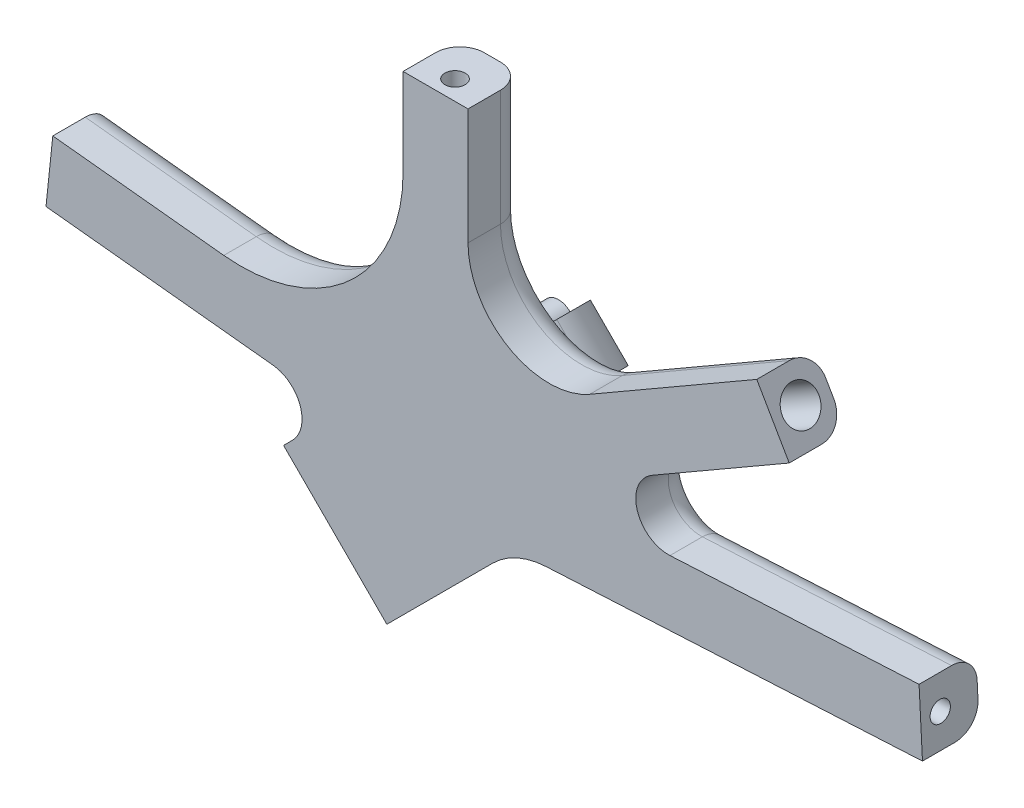
SolidWorks part; units mm, degrees
ref_plane "前基準面" through (0, 0, 0) normal (0, 0, 1) x (1, 0, 0)
ref_plane "上基準面" through (0, 0, 0) normal (0, 1, 0) x (1, 0, 0)
ref_plane "右基準面" through (0, 0, 0) normal (1, 0, 0) x (0, 0, -1)
sketch "草圖1" plane through (0, 0, 0) normal (0, 0, 1) x (1, 0, 0)
  line L0 (-27, 0) -> (-9.7279, 0) construction
  line L1 (-27, 2.7903) -> (-8.8458, 0.8822)
  line L2 (1.8837, -1.1163) -> (27, 0.2)
  line L3 (-27, 2.7903) -> (-26.5819, 6.7683)
  line L4 (-26.5819, 6.7683) -> (-5, 4.5)
  line L5 (3.1228, 2.9541) -> (26.7907, 4.1945)
  line L6 (26.7907, 4.1945) -> (27, 0.2)
  line L7 (-1, 5.1927) -> (16.7907, 15.4641)
  line L8 (16.7907, 15.4641) -> (18.7907, 12)
  line L9 (18.7907, 12) -> (3.1228, 2.9541)
  line L10 (-5, 4.5) -> (-5, 21)
  line L11 (-5, 21) -> (-1, 21)
  line L12 (-1, 21) -> (-1, 5.1927)
  line L13 (-8.8458, 0.8822) -> (-12.364, -2.636)
  line L14 (-12.364, -2.636) -> (-6, -9)
  line L15 (-6, -9) -> (1.8837, -1.1163)
  line L17 (3, 0) -> (27, 0) construction
  point P19 (-9.7279, 0)
  dimension "D1" = 54
  dimension "D2" = 27
  dimension "D3" = 6
  dimension "D4" = 3
  dimension "D5" = 90
  dimension "D6" = 4
  dimension "D7" = 4
  dimension "D8" = 4.5
  dimension "D9" = 4
  dimension "D10" = 30
  dimension "D11" = 8
  dimension "D12" = 12
  dimension "D13" = 4
  dimension "D14" = 22
  dimension "D15" = 135
  dimension "D16" = 90
  dimension "D17" = 9
  dimension "D18" = 21
  dimension "D19" = 16.5
  dimension "D20" = 0.2
  dimension "D21" = 9
extrude "填料-伸長1" add sketch "草圖1" along normal blind 3.5
fillet "圓角1" radius 5 2 edges at (1.8837, -1.1163, 1.75) (-1, 5.1927, 1.75)
fillet "圓角2" radius 2 2 edges at (-8.8458, 0.8822, 1.75) (3.1228, 2.9541, 1.75)
fillet "圓角3" radius 10 1 edges at (-5, 4.5, 1.75)
sketch "草圖2" plane through (-26.9951, 2.8373, 0) normal (-0.9945, 0.1045, 0) x (0, 0, 1)
  line L0 (3.5, 3.9527) -> (0, 3.9527) construction
  line L1 (3.5, 3.9527) -> (3.5, -0.0473) construction
  circle A0 centre (2.3, 1.9527) radius 0.625
  dimension "D1" = 1.25
  dimension "D2" = 2
  dimension "D3" = 1.2
extrude "除料-伸長1" cut sketch "草圖2" against normal blind 20
sketch "草圖3" plane through (0, 21, 0) normal (0, 1, 0) x (1, 0, 0)
  line L0 (-1, -3.5) -> (-1, 0) construction
  line L1 (-1, -3.5) -> (-5, -3.5) construction
  circle A0 centre (-3, -2.3) radius 0.625
  dimension "D2" = 1.25
  dimension "D1" = 2
  dimension "D3" = 1.2
extrude "除料-伸長2" cut sketch "草圖3" against normal blind 15
sketch "草圖4" plane through (19.2891, 11.1366, 0) normal (0.866, 0.5, 0) x (0, 0, -1)
  line L0 (-3.5, 4.997) -> (0, 4.997) construction
  line L1 (-3.5, 0.997) -> (-3.5, 4.997) construction
  circle A0 centre (-1.8, 2.997) radius 1.125
  point P2 (-1.75, 4.997)
  dimension "D2" = 2.25
  dimension "D1" = 2
  dimension "D3" = 1.7
extrude "除料-伸長3" cut sketch "草圖4" against normal blind 15
sketch "草圖5" plane through (26.9365, 1.4117, 0) normal (0.9986, 0.0523, 0) x (0, 0, -1)
  line L0 (0, 2.7867) -> (-3.5, 2.7867) construction
  line L1 (-3.5, -1.2133) -> (-3.5, 2.7867) construction
  circle A0 centre (-2.3, 0.7867) radius 0.625
  dimension "D2" = 1.25
  dimension "D1" = 2
  dimension "D3" = 1.2
extrude "除料-伸長4" cut sketch "草圖5" against normal blind 20
sketch "草圖6" plane through (0, 0, 0) normal (0, 0, -1) x (-1, 0, 0)
  line L0 (9.182, -5.818) -> (11.5154, -3.4846)
  line L1 (12.364, -2.636) -> (6, -9) construction
  line L2 (11.5154, -3.4846) -> (3.0302, 5.0007)
  line L3 (3.0302, 5.0007) -> (0.6967, 2.6673)
  line L4 (0.6967, 2.6673) -> (9.182, -5.818)
  line L5 (9.182, -5.818) -> (9.175, -6.0253)
  line L6 (6, -9) -> (-0.5265, -2.4735) construction
  line M17 (6, -9) -> (12.364, -2.636)
  dimension "D1" = 3.3
  dimension "D2" = 12
extrude "填料-伸長2" add sketch "草圖6" along normal blind 8 contours L3 L4 L2 M17 region at (-6.1061, -0.4087, 0)
sketch "草圖7" plane through (-1.682, 1.682, 0) normal (0.7071, -0.7071, 0) x (0, 0, -1)
  line L0 (8, -10.6066) -> (0, -10.6066) construction
  circle A0 centre (4, -8.6066) radius 1
  circle A2 centre (4, -0.6066) radius 1
  dimension "D1" = 2
  dimension "D6" = 2
  dimension "D2" = 2
  dimension "D3" = 4
  dimension "D4" = 8
extrude "除料-伸長6" cut sketch "草圖7" against normal up to next
fillet "圓角4" radius 4 1 edges at (-1.8634, 3.834, -8)
sketch "草圖8" plane through (-4.0154, 4.0154, 0) normal (-0.7071, 0.7071, 0) x (0, 0, 1)
  circle A0 centre (-4, -0.6066) radius 1.8
  circle A1 centre (-4, -8.6066) radius 1.8
  dimension "D1" = 3.6
  dimension "D2" = 3.6
extrude "除料-伸長7" cut sketch "草圖8" against normal blind 0.5
fillet "圓角5" radius 1.5 15 edges at (-12.0873, -2.3594, 0) (-11.3396, -0.001, 0) (-21.3136, 6.2146, 0) (-5, 18.3031, 0) (-1, 17.4265, 0) (1.5, 9.5228, 0) (14.564, 9.5597, 0) (9.4196, 4.8194, 0) (-2.7367, -5.7367, 0) (2.0284, -1.4413, 0) (-20.0079, 2.0554, 0) (-8.3087, 8.1747, 0) (11.6453, 12.4934, 0) (19.1163, 3.7923, 0) (15.4002, -0.4079, 0)
sketch "草圖9" plane through (-4.0154, 4.0154, 0) normal (-0.7071, 0.7071, 0) x (0, 0, 1)
  line L0 (-8, -10.6066) -> (-8, -2.6066) construction
  line L1 (-8, -3.1066) -> (0, -3.1066)
  line L2 (-8, -3.1066) -> (-8, -6.1066)
  line L3 (-8, -6.1066) -> (0, -6.1066)
  line L4 (0, -3.1066) -> (0, -6.1066)
  line L5 (0, -8.4064) -> (0, 1.3934) construction
  circle A0 centre (-4, -0.6066) radius 1 construction
  circle A1 centre (-4, -8.6066) radius 1 construction
  dimension "D1" = 2.5
  dimension "D2" = 2.5
extrude "填料-伸長3" add sketch "草圖9" along normal blind 1
fillet "圓角6" radius 1 2 edges at (-9.0406, 0.4045, -4) (-6.9192, 2.5258, -4)
